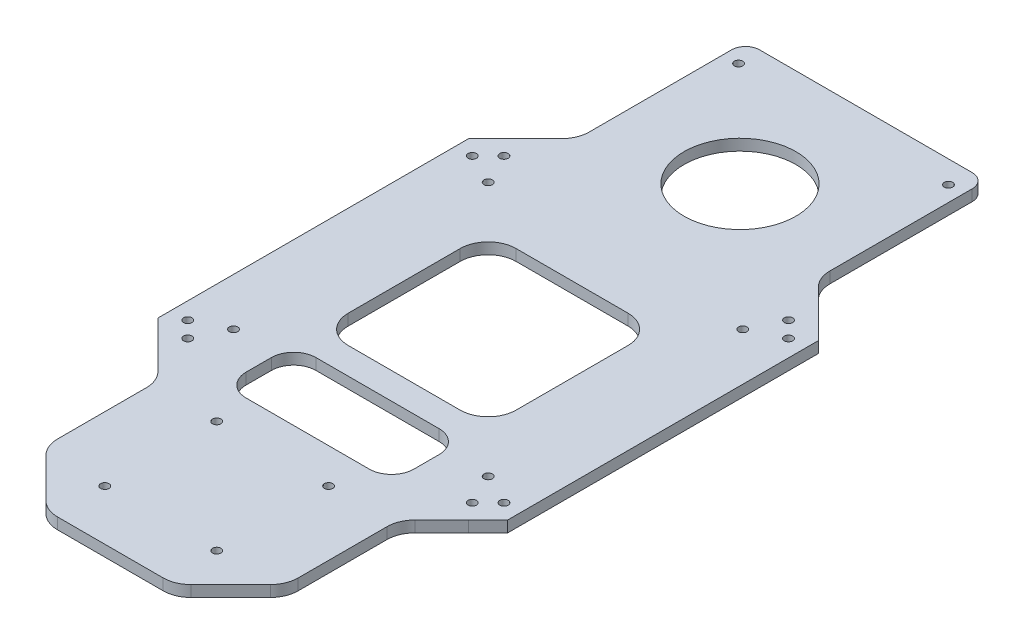
SolidWorks part; units mm, degrees
material "Thornel Mat VMA"
ref_plane "前视基准面" through (0, 0, 0) normal (0, 0, 1) x (1, 0, 0)
ref_plane "上视基准面" through (0, 0, 0) normal (0, 1, 0) x (1, 0, 0)
ref_plane "右视基准面" through (0, 0, 0) normal (1, 0, 0) x (0, 0, -1)
other "Configuration Table"
sketch "草图1" plane through (0, 0, 0) normal (0, 1, 0) x (1, 0, 0)
  line L0 (0, 0) -> (63.1315, 0) construction
  line L1 (-62.5, -62.5) -> (62.5, -62.5)
  line L2 (-62.5, -62.5) -> (-62.5, 62.5)
  line L3 (-62.5, 62.5) -> (62.5, 62.5)
  line L4 (62.5, -62.5) -> (62.5, 62.5)
  line L5 (-62.5, -62.5) -> (62.5, 62.5) construction
  line L6 (-62.5, 62.5) -> (62.5, -62.5) construction
  line L7 (0, 0) -> (0, 71.086) construction
  line L8 (50.8431, 56.5) -> (56.5, 50.8431) construction
  line L9 (43, 62.5) -> (43, 135)
  line L10 (43, 135) -> (-43, 135)
  line L11 (-43, 62.5) -> (-43, 135)
  line L12 (-43, -62.5) -> (-43, -135)
  line L13 (43, -135) -> (-43, -135)
  line L14 (43, -62.5) -> (43, -135)
  circle A4 centre (50.8431, 56.5) radius 1.5
  circle A5 centre (56.5, 50.8431) radius 1.5
  circle A6 centre (56.5, -50.8431) radius 1.5
  circle A7 centre (50.8431, -56.5) radius 1.5
  circle A8 centre (-50.8431, -56.5) radius 1.5
  circle A9 centre (-56.5, -50.8431) radius 1.5
  circle A10 centre (-56.5, 50.8431) radius 1.5
  circle A11 centre (-50.8431, 56.5) radius 1.5
  circle A12 centre (-37.5, 127) radius 1.5
  circle A13 centre (37.5, 127) radius 1.5
  point P0 (0, 0)
  point P14 (0, 135)
  point P42 (0, -135)
  dimension "D3" = 72.5
  dimension "D5" = 3
  dimension "D6" = 3
  dimension "D7" = 3
  dimension "D8" = 8
  dimension "D13" = 75
  dimension "D1" = 125
  dimension "D2" = 125
  dimension "D4" = 86
  dimension "D9" = 45
  dimension "D10" = 6
  dimension "D11" = 6
  dimension "D12" = 127
extrude "凸台-拉伸1" add sketch "草图1" along normal blind 4 contours L1 L4 L3 L2 A10 A9 A8 A6 A5 A4 A7 A11 | L11 L3 L9 L10 | L14 L1 L12 L13 region at (0, 0, 0) region at (0, 0, 98.75) region at (0, 0, -98.6858)
chamfer "倒角1" distance 7 angle 45 4 edges at (-62.5, 2, 62.5) (-62.5, 2, -62.5) (62.5, 2, 62.5) (62.5, 2, -62.5)
sketch "草图3" plane through (0, 4, 0) normal (0, 1, 0) x (1, 0, 0)
  line L0 (0, 0) -> (95.6793, 0) construction
  line L1 (0, 0) -> (0, 105.8926) construction
  line L18 (-49.5, -49.5) -> (49.5, -49.5)
  line L19 (-49.5, -49.5) -> (-49.5, 49.5)
  line L20 (-49.5, 49.5) -> (49.5, 49.5)
  line L21 (49.5, -49.5) -> (49.5, 49.5)
  line L22 (-49.5, -49.5) -> (49.5, 49.5) construction
  line L23 (-49.5, 49.5) -> (49.5, -49.5) construction
  line L24 (-30, -30) -> (30, -30)
  line L25 (-30, -30) -> (-30, 30)
  line L26 (-30, 30) -> (30, 30)
  line L27 (30, -30) -> (30, 30)
  line L28 (-30, -30) -> (30, 30) construction
  line L29 (-30, 30) -> (30, -30) construction
  line L34 (0, -97) -> (73.0056, -97) construction
  line L36 (0, 0) -> (0, -149.5176) construction
  line L39 (-30, -39.5) -> (-30, -59.5)
  line L48 (-30, -39.5) -> (30, -39.5)
  line L49 (30, -39.5) -> (30, -59.5)
  line L50 (-30, -59.5) -> (30, -59.5)
  line L51 (-30, -59.5) -> (-30, -64.5)
  line L52 (-30, -64.5) -> (30, -64.5)
  line L53 (30, -64.5) -> (30, -59.5)
  circle A4 centre (-45.5, 45.5) radius 1.5
  circle A5 centre (45.5, 45.5) radius 1.5
  circle A6 centre (45.5, -45.5) radius 1.5
  circle A7 centre (-45.5, -45.5) radius 1.5
  circle A8 centre (0, 90) radius 20
  circle A9 centre (-20, -117) radius 1.5
  circle A10 centre (20, -117) radius 1.5
  circle A11 centre (20, -77) radius 1.5
  circle A12 centre (-20, -77) radius 1.5
  point P24 (-30, -49.5)
  point P26 (0, -59.5)
  point P30 (0, -39.5)
  dimension "D14" = 40
  dimension "D15" = 40
  dimension "D3" = 3
  dimension "D7" = 40
  dimension "D8" = 90
  dimension "D12" = 3
  dimension "D1" = 99
  dimension "D2" = 99
  dimension "D4" = 4
  dimension "D5" = 60
  dimension "D6" = 60
  dimension "D9" = 10
  dimension "D10" = 30
  dimension "D11" = 5
  dimension "D13" = 97
extrude "切除-拉伸1" cut sketch "草图3" against normal blind 4 contours L24 L27 L26 L25 | A4 | A5 | A6 | A7 | A8 | L49 L48 L39 L18 | L39 L50 L49 L18 | L52 L53 L50 L51 | A12 | A11 | A10 | A9 region at (0, 4, 44.5) region at (0, 4, 54.5) region at (0, 4, 62) region at (0, 4, 0) region at (-45.5, 4, -45.5) region at (45.5, 4, -45.5) region at (45.5, 4, 45.5) region at (-45.5, 4, 45.5) region at (0, 4, -90) region at (20, 4, 117) region at (20, 4, 77) region at (-20, 4, 77)
fillet "圆角3" radius 10 4 edges at (-30, 2, 30) (30, 2, 30) (30, 2, -30) (-30, 2, -30)
sketch "草图4" plane through (0, 4, 0) normal (0, 1, 0) x (1, 0, 0)
  line L0 (0, 0) -> (147.6965, 0) construction
  line L1 (0, 0) -> (0, 135.7677) construction
  line L2 (-50, 45) -> (70.2761, 45) construction
  line L7 (-50, 45) -> (-50, -77.0358) construction
  circle A0 centre (-41, 32.5) radius 1.5
  circle A1 centre (44, 30) radius 1.5
  circle A2 centre (-39, -27) radius 1.5
  circle A3 centre (39, -27) radius 1.5
  dimension "D1" = 3
  dimension "D3" = 12.5
  dimension "D5" = 3
  dimension "D8" = 3
  dimension "D10" = 3
  dimension "D12" = 72
  dimension "D2" = 9
  dimension "D4" = 94
  dimension "D6" = 15
  dimension "D7" = 11
  dimension "D9" = 72
  dimension "D11" = 89
  dimension "D13" = 50
  dimension "D14" = 45
fillet "圆角4" radius 5 2 edges at (43, 2, -135) (-43, 2, -135)
fillet "圆角5" radius 8 4 edges at (-30, 2, 64.5) (30, 2, 64.5) (30, 2, 39.5) (-30, 2, 39.5)
chamfer "倒角2" distance 12.5 angle 45 4 edges at (43, 2, -62.5) (-43, 2, -62.5) (43, 2, 62.5) (-43, 2, 62.5)
fillet "圆角6" radius 10 4 edges at (-43, 2, -75) (43, 2, -75) (43, 2, 75) (-43, 2, 75)
chamfer "倒角3" distance 20 angle 45 2 edges at (43, 2, 135) (-43, 2, 135)
fillet "圆角7" radius 10 4 edges at (43, 2, 115) (23, 2, 135) (-23, 2, 135) (-43, 2, 115)
